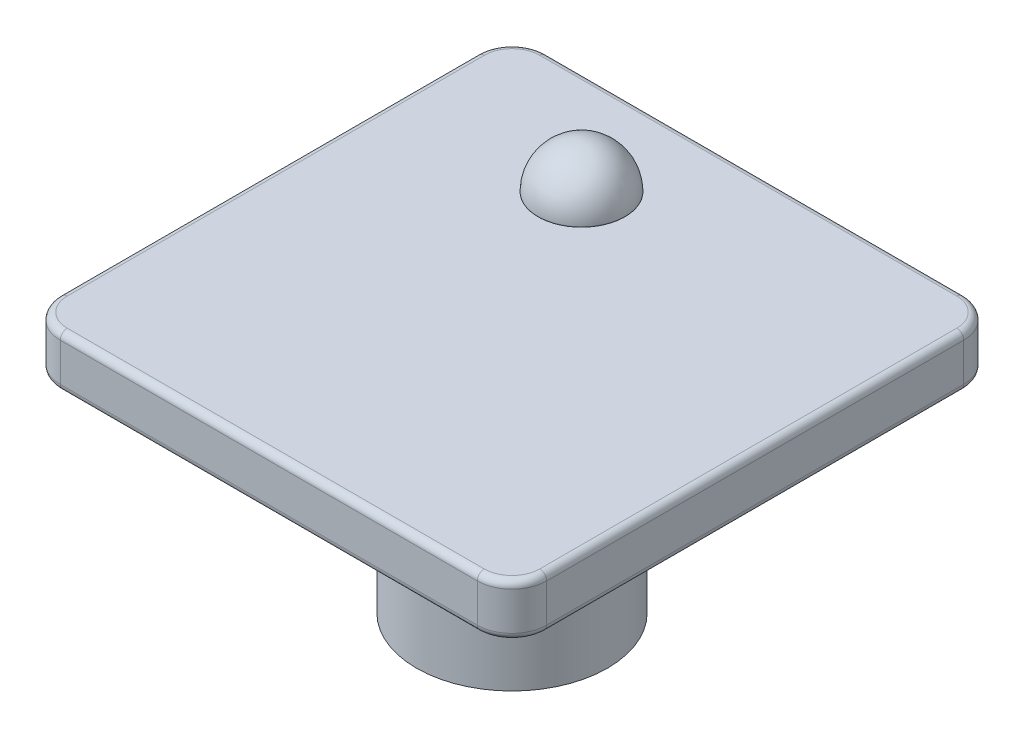
SolidWorks part; units mm, degrees
ref_plane "Front Plane" through (0, 0, 0) normal (0, 0, 1) x (1, 0, 0)
ref_plane "Top Plane" through (0, 0, 0) normal (0, 1, 0) x (1, 0, 0)
ref_plane "Right Plane" through (0, 0, 0) normal (1, 0, 0) x (0, 0, -1)
sketch "Sketch1" plane through (0, 0, 0) normal (0, 1, 0) x (1, 0, 0)
  line L1 (-7.3247, 4.3967) -> (4.6753, 4.3967)
  line L2 (-8.3247, 3.3967) -> (-8.3247, -8.6033)
  line L3 (-7.3247, -9.6033) -> (4.6753, -9.6033)
  line L4 (5.6753, 3.3967) -> (5.6753, -8.6033)
  arc A0 (-8.3247, -8.6033) -> (-7.3247, -9.6033) centre (-7.3247, -8.6033) ccw
  arc A1 (4.6753, -9.6033) -> (5.6753, -8.6033) centre (4.6753, -8.6033) ccw
  arc A2 (4.6753, 4.3967) -> (5.6753, 3.3967) centre (4.6753, 3.3967) cw
  arc A3 (-7.3247, 4.3967) -> (-8.3247, 3.3967) centre (-7.3247, 3.3967) ccw
  point P8 (5.6753, -9.6033)
  point P11 (5.6753, 4.3967)
  point P14 (-8.3247, 4.3967)
  dimension "D3" = 1
  dimension "D1" = 14
  dimension "D2" = 14
extrude "Boss-Extrude1" add sketch "Sketch1" along normal blind 1.5
sketch "Sketch2" plane through (0, 0, 0) normal (0, -1, 0) x (1, 0, 0)
  line L0 (-7.3247, 9.6033) -> (4.6753, 9.6033) construction
  line L1 (5.6753, 8.6033) -> (5.6753, -3.3967) construction
  line L2 (-1.3247, -4.3967) -> (-1.3247, 9.6033) construction
  line L3 (-8.3247, 2.6033) -> (5.6753, 2.6033) construction
  line L4 (-8.3247, -3.3967) -> (-8.3247, 8.6033) construction
  circle A0 centre (-1.3247, 2.6033) radius 2.75
  dimension "D1" = 7
  dimension "D2" = 7
extrude "Boss-Extrude2" add sketch "Sketch2" along normal blind 6
sketch "Sketch3" plane through (0, -6, 0) normal (0, -1, 0) x (1, 0, 0)
  line L0 (-1.3247, 5.3533) -> (-1.3247, -0.1467) construction
  line L1 (-3.3247, 3.1533) -> (0.6753, 3.1533)
  line L2 (-3.3247, 3.1533) -> (-3.3247, 2.0533)
  line L3 (-3.3247, 2.0533) -> (0.6753, 2.0533)
  line L4 (0.6753, 3.1533) -> (0.6753, 2.0533)
  line L5 (-1.8747, 4.6033) -> (-0.7747, 4.6033)
  line L6 (-1.8747, 4.6033) -> (-1.8747, 0.6033)
  line L7 (-1.8747, 0.6033) -> (-0.7747, 0.6033)
  line L8 (-0.7747, 4.6033) -> (-0.7747, 0.6033)
  line L9 (-4.0747, 2.6033) -> (1.4253, 2.6033) construction
  circle A3 centre (-1.3247, 2.6033) radius 2.75 construction
  circle A4 centre (-1.3247, 2.6033) radius 2.75 construction
  dimension "D7" = 0.55
  dimension "D1" = 4
  dimension "D2" = 1.1
  dimension "D3" = 1.1
  dimension "D4" = 4
  dimension "D5" = 2
  dimension "D6" = 2
  dimension "D8" = 0.55
extrude "Cut-Extrude1" cut sketch "Sketch3" against normal blind 6 contours L8 L5 L6 L1 | L1 L8 L3 L4 | L8 L1 L6 L3 | L6 L1 L2 L3 | L8 L3 L6 L7 region at (-2.5997, -6, 2.6033) region at (-1.3247, -6, 3.8783) region at (-1.3247, -6, 2.6033) region at (-0.0497, -6, 2.6033) region at (-1.3247, -6, 1.3283)
chamfer "Chamfer1" distance 0.3 angle 45 12 edges at (-1.3247, -6, 0.6033) (-1.8747, -6, 1.3283) (-2.5997, -6, 2.0533) (-3.3247, -6, 2.6033) (-2.5997, -6, 3.1533) (-0.7747, -6, 1.3283) (-0.0497, -6, 2.0533) (0.6753, -6, 2.6033) (-0.0497, -6, 3.1533) (-0.7747, -6, 3.8783) (-1.3247, -6, 4.6033) (-1.8747, -6, 3.8783)
fillet "Fillet1" radius 1 1 edges at (-1.3247, 0, -0.1467)
sketch "Sketch4" plane through (0, 1.5, 0) normal (0, 1, 0) x (1, 0, 0)
  line L0 (-1.3247, 4.3967) -> (-1.3247, -9.6033) construction
  line L1 (4.6753, 4.3967) -> (-7.3247, 4.3967) construction
  line L2 (-7.3247, -9.6033) -> (4.6753, -9.6033) construction
  line L3 (5.6753, -2.6033) -> (-8.3247, -2.6033) construction
  line L4 (-8.3247, 3.3967) -> (-8.3247, -8.6033) construction
  line L5 (5.6753, -8.6033) -> (5.6753, 3.3967) construction
  line L6 (-3.3247, 4.3967) -> (-3.3247, -9.6033) construction
  line L7 (0.6753, 4.3967) -> (0.6753, -9.6033) construction
  line L8 (-8.3247, 1.3967) -> (5.6753, 1.3967) construction
  line L9 (5.6753, -6.6033) -> (-8.3247, -6.6033) construction
  circle A0 centre (-3.3247, 1.3967) radius 1.25
  dimension "D1" = 4
  dimension "D2" = 4
  dimension "D3" = 2
  dimension "D4" = 2
extrude "Boss-Extrude3" add sketch "Sketch4" along normal blind 0.01
dome "Dome1" faces to dome 1 distance 1.25 reverse direction no elliptical dome no face at (-3.3247, 1.51, -0.1467) parameters "D1"=1.25
fillet "Fillet3" radius 0.2 16 edges at (5.3824, 1.5, -4.1038) (5.6753, 1.5, 2.6033) (5.3824, 1.5, 9.3104) (-1.3247, 1.5, 9.6033) (-8.0318, 1.5, 9.3104) (-8.0318, 1.5, -4.1038) (-8.3247, 1.5, 2.6033) (-1.3247, 1.5, -4.3967) (5.3824, 0, 9.3104) (5.6753, 0, 2.6033) (5.3824, 0, -4.1038) (-1.3247, 0, -4.3967) (-8.0318, 0, -4.1038) (-8.3247, 0, 2.6033) (-8.0318, 0, 9.3104) (-1.3247, 0, 9.6033)
